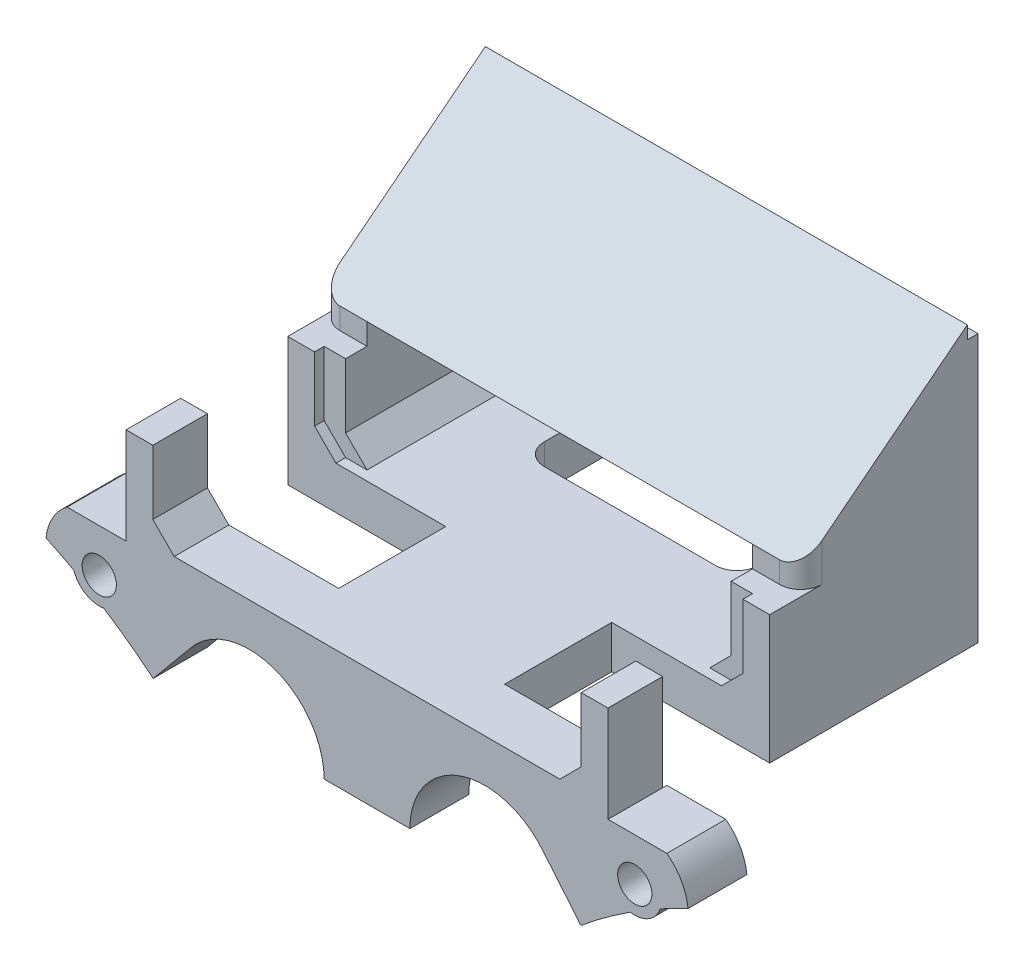
SolidWorks part; units mm, degrees
ref_plane "前视基准面" through (0, 0, 0) normal (0, 0, 1) x (1, 0, 0)
ref_plane "上视基准面" through (0, 0, 0) normal (0, 1, 0) x (1, 0, 0)
ref_plane "右视基准面" through (0, 0, 0) normal (1, 0, 0) x (0, 0, -1)
sketch "草图1" plane through (0, 0, 0) normal (0, 0, 1) x (1, 0, 0)
  line L0 (0, 0) -> (22.5, 0)
  line L1 (22.5, 0) -> (22.5, 12)
  line L2 (22.5, 12) -> (-22.5, 12)
  line L3 (-22.5, 12) -> (-22.5, 0)
  line L4 (-22.5, 0) -> (0, 0)
extrude "凸台-拉伸1" add sketch "草图1" along normal blind 34.55
sketch "草图2" plane through (0, 0, 34.55) normal (0, 0, 1) x (1, 0, 0)
  line L0 (-20, 12) -> (20, 12)
  line L1 (22.5, 12) -> (-22.5, 12) construction
  line L2 (20, 12) -> (20, 4)
  line L3 (20, 4) -> (-20, 4)
  line L4 (0, -6.6) -> (0, 6.6) construction
  line L5 (-20, 12) -> (-20, 4)
  point P9 (0, 4)
  point P10 (0, 12)
extrude "切除-拉伸1" cut sketch "草图2" against normal blind 16
chamfer "倒角1" distance 2 angle 45 2 edges at (20, 4, 26.55) (-20, 4, 26.55)
sketch "草图6" plane through (0, 12, 0) normal (0, 1, 0) x (1, 0, 0)
  line L0 (22.5, 0) -> (22.5, -13.5)
  line L2 (22.5, -34.55) -> (22.5, 0) construction
  line L3 (22.5, -13.5) -> (17, -13.5)
  line L4 (14.5, -11) -> (14.5, -5)
  line L5 (14.5, -5) -> (14.5, 0)
  line L6 (22.5, 0) -> (-22.5, 0) construction
  line L7 (14.5, 0) -> (22.5, 0)
  line L8 (0, -10.45) -> (0, 10.45) construction
  line L9 (-14.5, 0) -> (-22.5, 0)
  line L10 (-14.5, -5) -> (-14.5, 0)
  line L11 (-14.5, -11) -> (-14.5, -5)
  line L12 (-22.5, -13.5) -> (-17, -13.5)
  line L13 (-22.5, 0) -> (-22.5, -13.5)
  circle A0 centre (17, -5) radius 1.6
  circle A1 centre (17, -11) radius 1.6
  arc A2 (17, -13.5) -> (14.5, -11) centre (17, -11) cw
  arc A3 (-17, -13.5) -> (-14.5, -11) centre (-17, -11) ccw
  circle A4 centre (-17, -11) radius 1.6
  circle A5 centre (-17, -5) radius 1.6
extrude "凸台-拉伸2" add sketch "草图6" against normal blind 6.9
sketch "草图8" plane through (0, 0, 34.55) normal (0, 0, 1) x (1, 0, 0)
  line L1 (1.843, -25.3671) -> (9.2306, -19.6151)
  line L2 (-18, 4) -> (18, 4) construction
  line L3 (0, -10.45) -> (0, 10.45) construction
  line L5 (16.5232, -2.6996) -> (19.968, -6.8465)
  line L6 (-1.843, -25.3671) -> (-9.2306, -19.6151)
  line L7 (-5.4768, -11.3004) -> (-10.4216, -17.6514)
  line L8 (5.4768, -11.3004) -> (10.4216, -17.6514)
  line L9 (-16.5232, -2.6996) -> (-19.968, -6.8465)
  line L10 (22.5, 3) -> (22.5, 4)
  line L11 (-22.5, 12) -> (-22.5, 0) construction
  line L12 (-22.5, 3) -> (-28, 3)
  line L13 (-22.5, 3) -> (-22.5, 4)
  line L14 (22.5, 3) -> (28, 3)
  line L15 (-22.5, 4) -> (22.5, 4)
  circle A1 centre (25, -1) radius 1.6
  circle A3 centre (0, -23) radius 1.6
  arc A4 (-1.843, -25.3671) -> (1.843, -25.3671) centre (0, -23) ccw
  circle A6 centre (-25, -1) radius 1.6
  arc A8 (29.9729, -0.4804) -> (27.3654, -1.8093) centre (50, -43) ccw
  arc A9 (10.4216, -17.6514) -> (9.2306, -19.6151) centre (50, -43) ccw
  arc A10 (16.5232, -2.6996) -> (5.4768, -11.3004) centre (11, -7) ccw
  arc A11 (24.5837, -3.4651) -> (27.3654, -1.8093) centre (25, -1) ccw
  arc A12 (24.5837, -3.4651) -> (19.968, -6.8465) centre (50, -43) ccw
  arc A13 (-10.4216, -17.6514) -> (-9.2306, -19.6151) centre (-50, -43) cw
  arc A14 (-16.5232, -2.6996) -> (-5.4768, -11.3004) centre (-11, -7) cw
  arc A15 (-24.5837, -3.4651) -> (-19.968, -6.8465) centre (-50, -43) cw
  arc A16 (-24.5837, -3.4651) -> (-27.3654, -1.8093) centre (-25, -1) cw
  arc A17 (-29.9729, -0.4804) -> (-27.3654, -1.8093) centre (-50, -43) cw
  arc A18 (-29.9729, -0.4804) -> (-28, 3) centre (-25, -1) cw
  arc A19 (29.9729, -0.4804) -> (28, 3) centre (25, -1) ccw
  point P23 (0, 4)
extrude "凸台-拉伸3" add sketch "草图8" against normal blind 5.5
sketch "草图11" plane through (0, 0, 29.05) normal (0, 0, -1) x (-1, 0, 0)
  line L0 (-4, -7) -> (4, -7)
  line L1 (-4, -7) -> (-10.4216, -17.6514)
  line L2 (-10.4216, -17.6514) -> (-10.4216, -27.0892)
  line L3 (-10.4216, -27.0892) -> (10.4216, -27.0892)
  line L4 (0, 19.0025) -> (0, -19.0025) construction
  line L5 (10.4216, -17.6514) -> (10.4216, -27.0892)
  line L6 (4, -7) -> (10.4216, -17.6514)
  arc A0 (-5.4768, -11.3004) -> (-11, 0) centre (-11, -7) ccw construction
  arc A1 (11, 0) -> (5.4768, -11.3004) centre (11, -7) ccw construction
  point P16 (0, -27.0892)
extrude "切除-拉伸6" cut sketch "草图11" against normal blind 10
sketch "草图12" plane through (0, 0, 18.55) normal (0, 0, 1) x (1, 0, 0)
  line L0 (-18, 6) -> (-16, 4)
  line L1 (20, 12) -> (-20, 12) construction
  line L4 (-18, 6) -> (-18, 12)
  line L5 (-18, 4) -> (18, 4) construction
  line L6 (-16, 4) -> (16, 4)
  line L7 (-18, 4) -> (18, 4) construction
  line L8 (0, -19.0025) -> (0, 19.0025) construction
  line L9 (18, 6) -> (18, 12)
  line L10 (18, 6) -> (16, 4)
  line L11 (-18, 12) -> (18, 12)
  point P15 (0, 4)
extrude "切除-拉伸7" cut sketch "草图12" against normal blind 25
sketch "草图13" plane through (0, 4, 0) normal (0, 1, 0) x (1, 0, 0)
  line L9 (-22.5, -34.55) -> (-22.5, 0) construction
  line L11 (-7.75, -24.45) -> (-7.75, -28.45)
  line L12 (-22.5, -24.45) -> (-22.5, -28.45)
  line L18 (-7.75, -28.45) -> (-7.75, -29.45)
  line L19 (-7.75, -29.45) -> (-22.5, -29.45)
  line L20 (-22.5, -29.05) -> (-22.5, -34.55) construction
  line L21 (-22.5, -29.45) -> (-22.5, -28.45)
  line L24 (-22.5, -21.45) -> (-22.5, -24.45)
  line L34 (-7.75, -24.45) -> (-7.75, -19.45)
  line L35 (-7.75, -19.45) -> (-22.5, -19.45)
  line L36 (-22.5, -19.45) -> (-22.5, -21.45)
  line L37 (0, -19.0025) -> (0, 19.0025) construction
  line L38 (22.5, -19.45) -> (22.5, -21.45)
  line L39 (7.75, -19.45) -> (22.5, -19.45)
  line L40 (7.75, -24.45) -> (7.75, -19.45)
  line L41 (22.5, -21.45) -> (22.5, -24.45)
  line L42 (22.5, -29.45) -> (22.5, -28.45)
  line L43 (7.75, -29.45) -> (22.5, -29.45)
  line L44 (7.75, -28.45) -> (7.75, -29.45)
  line L45 (22.5, -24.45) -> (22.5, -28.45)
  line L46 (7.75, -24.45) -> (7.75, -28.45)
extrude "切除-拉伸8" cut sketch "草图13" against normal blind 25 and the other way blind 25
sketch "草图14" plane through (0, 4, 0) normal (0, 1, 0) x (1, 0, 0)
  line L1 (-10, -10) -> (10, -10)
  line L2 (10, -10) -> (10, 0)
  line L3 (-16, 0) -> (16, 0) construction
  line L4 (10, 0) -> (-10, 0)
  line L5 (-10, -10) -> (-10, 0)
extrude "切除-拉伸9" cut sketch "草图14" against normal blind 25
fillet "圆角1" radius 2 4 edges at (-10, 2, 0) (10, 2, 0) (10, 2, 10) (-10, 2, 10)
sketch "草图15" plane through (-22.5, 0, 0) normal (-1, 0, 0) x (0, 0, 1)
  line L0 (0, 12) -> (16.55, 12)
  line L1 (19.45, 12) -> (0, 12) construction
  line L2 (16.55, 12) -> (16.55, 14)
  line L5 (0, 12) -> (0, 27)
  line L6 (0, 27) -> (16.55, 14)
extrude "凸台-拉伸4" add sketch "草图15" against normal up to surface (45 mm away) up to face at (22.5, 6, 9.725)
sketch "草图16" plane through (-22.5, 0, 0) normal (-1, 0, 0) x (0, 0, 1)
  line L0 (0, 12) -> (14, 12)
  line L3 (14, 13.8499) -> (14, 12)
  line L4 (14, 13.8499) -> (0, 24.8469)
  line L5 (0, 27) -> (0, 0) construction
  line L6 (16.55, 14) -> (0, 27) construction
  line L7 (0, 24.8469) -> (0, 12)
extrude "切除-拉伸10" cut sketch "草图16" against normal up to surface (40.5 mm away) from offset 4.5 up to face at (18, 9.6, 10.73) offset against normal yes
sketch "草图17" plane through (0, 0, 16.55) normal (0, 0, 1) x (1, 0, 0)
  line L0 (-18, 12) -> (-18, 14)
  line L1 (22.5, 14) -> (-22.5, 14) construction
  line L3 (18, 12) -> (18, 14)
  line L4 (18, 14) -> (-18, 14)
  line L5 (-18, 12) -> (18, 12)
extrude "切除-拉伸11" cut sketch "草图17" against normal blind 25
sketch "草图18" plane through (-22.5, 0, 0) normal (-1, 0, 0) x (0, 0, 1)
  line L1 (0, 27) -> (0, 0) construction
  line L3 (0, 25) -> (1, 25)
  line L4 (1, 25) -> (1, 26.2145)
  line L5 (16.55, 14) -> (0, 27) construction
  line L6 (0, 25) -> (0, 27)
  line L7 (0, 27) -> (1, 26.2145)
extrude "切除-拉伸12" cut sketch "草图18" against normal up to next
fillet "圆角2" radius 2 2 edges at (22.5, 13, 16.55) (-22.5, 13, 16.55)
